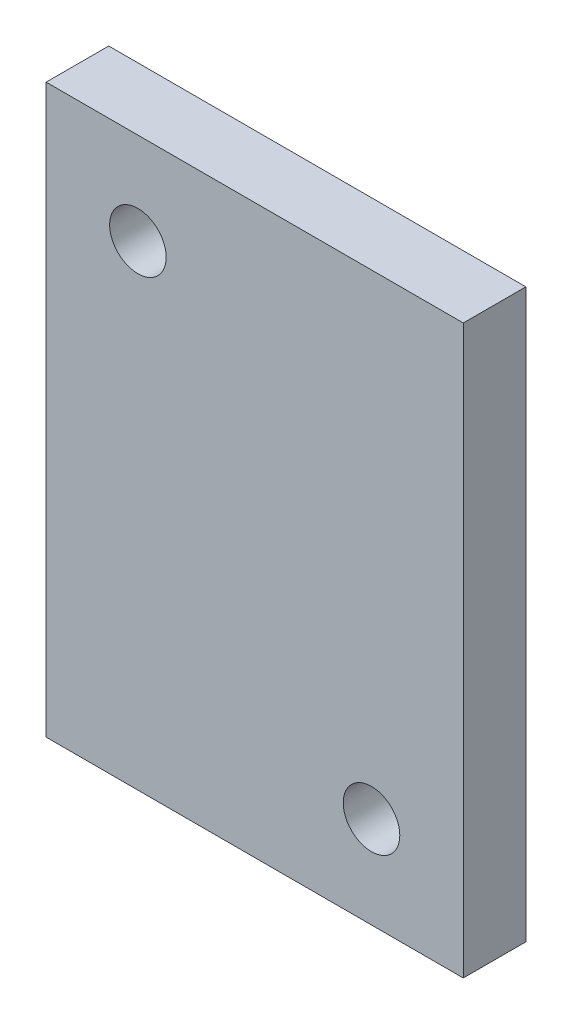
SolidWorks part; units mm, degrees
ref_plane "Front Plane" through (0, 0, 0) normal (0, 0, 1) x (1, 0, 0)
ref_plane "Top Plane" through (0, 0, 0) normal (0, 1, 0) x (1, 0, 0)
ref_plane "Right Plane" through (0, 0, 0) normal (1, 0, 0) x (0, 0, -1)
sketch "Sketch1" plane through (0, 0, 0) normal (0, 0, 1) x (1, 0, 0)
  line L4 (-3101.1588, 1119.8207) -> (-3101.1588, 1076.6407)
  line L5 (-3101.1588, 1076.6407) -> (-3069.4088, 1076.6407)
  line L6 (-3069.4088, 1076.6407) -> (-3069.4088, 1119.8207)
  line L7 (-3069.4088, 1119.8207) -> (-3101.1588, 1119.8207)
  line L8 (-3101.1588, 1119.8207) -> (-3101.1588, 1076.6407)
  line L9 (-3101.1588, 1076.6407) -> (-3069.4088, 1076.6407)
  line L10 (-3069.4088, 1076.6407) -> (-3069.4088, 1119.8207)
  line L11 (-3069.4088, 1119.8207) -> (-3101.1588, 1119.8207)
  dimension "D1" = 0
extrude "Boss-Extrude1" add sketch "Sketch1" along normal blind 4.7625
hole_wizard "#6 Clearance Hole1" positions "Sketch3" profile "Sketch2" hole size "#6" standard "ANSI Inch" end condition through all
sketch "Sketch3" plane through (0, 0, 4.7625) normal (0, 0, 1) x (1, 0, 0)
  point P0 (-3076.3938, 1083.6257)
  point P3 (-3094.1738, 1112.8357)
sketch "Sketch2" plane through (-3076.3938, 1083.6257, 4.7625) normal (1, 0, 0) x (0, -1, 0)
  line L0 (0, 0) -> (0, 4.7625)
  line L1 (0, 4.7625) -> (2.1526, 4.7625)
  line L2 (2.1526, 4.7625) -> (2.1526, 0)
  line L5 (2.1526, 0) -> (0, 0)
  line L11 (0, -6.35) -> (0, 107.95) construction
  dimension "Thru Hole Dia." = 4.3053
  dimension "Thru Hole Depth" = 4.7625
